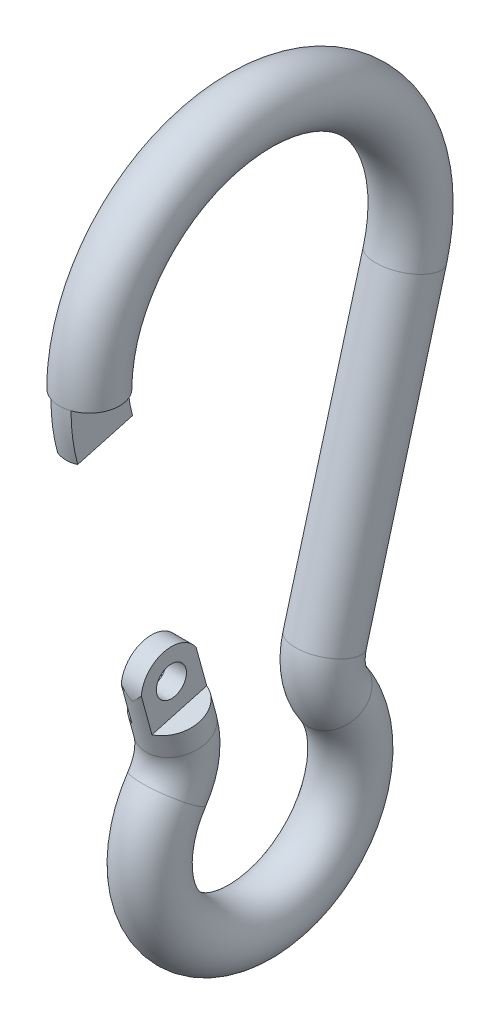
SolidWorks part; units mm, degrees
material "AISI 1020"
ref_plane "Front Plane" through (0, 0, 0) normal (0, 0, 1) x (1, 0, 0)
ref_plane "Top Plane" through (0, 0, 0) normal (0, 1, 0) x (1, 0, 0)
ref_plane "Right Plane" through (0, 0, 0) normal (1, 0, 0) x (0, 0, -1)
sketch "Sketch1" plane through (0, 0, 0) normal (1, 0, 0) x (0, 0, -1)
  line L0 (15.9242, -4.3589) -> (5.7761, -41.4323)
  line L1 (-5.7761, -41.4323) -> (-8.5475, -31.3076)
  line L2 (0, 0) -> (-16.51, 0) construction
  arc A0 (-15.9242, -4.3589) -> (-16.51, 0) centre (0, 0) cw
  arc A1 (5.7761, -41.4323) -> (7.3502, -50.8794) centre (16.8005, -44.45) ccw
  arc A2 (7.3502, -50.8794) -> (-7.3502, -50.8794) centre (0, -55.88) cw
  arc A3 (-7.3502, -50.8794) -> (-5.7761, -41.4323) centre (-16.8005, -44.45) ccw
  arc A4 (-16.51, 0) -> (15.9242, -4.3589) centre (0, 0) cw
  point P11 (-4.5087, 9.6726)
  point P15 (0, 0)
  point P16 (0, 0)
  point P17 (0, 0)
  point P18 (0, 0)
  point P19 (0, 0)
  point P20 (0, 0)
  dimension "D1" = 16.51
  dimension "D4" = 11.43
  dimension "D5" = 8.89
  dimension "D2" = 44.45
  dimension "D3" = 11.43
  dimension "D6" = 27.94
sketch "Sketch2" plane through (0, 0, 0) normal (0, 0, 1) x (1, 0, 0)
  circle A0 centre (0, 20.32) radius 3.81
  point P2 (0, 0)
  dimension "D2" = 7.62
  dimension "D1" = 16.51
sweep "Sweep1" add profiles "Sketch2" path "Sketch1"
sketch "Sketch7" plane through (0, 0, 0) normal (1, 0, 0) x (0, 0, -1)
  line L0 (-24.13, 0) -> (-16.51, 0)
  line L1 (-23.2738, -6.3708) -> (-15.9242, -4.3589)
  line L2 (-15.8972, -33.3194) -> (-8.5475, -31.3076)
  line L3 (-8.5475, -31.3076) -> (-7.5416, -34.9824)
  line L4 (-15.8972, -33.3194) -> (-14.8912, -36.9942)
  line L5 (-11.2164, -35.9883) -> (-14.8912, -36.9942) construction
  line L6 (-14.8912, -36.9942) -> (-13.8853, -40.669)
  line L7 (-15.8972, -33.3194) -> (-13.1257, -43.4441) construction
  line L8 (-13.8853, -40.669) -> (-6.5357, -38.6572)
  line L9 (-5.7761, -41.4323) -> (-8.5475, -31.3076) construction
  line L10 (-6.5357, -38.6572) -> (-7.5416, -34.9824)
  line L11 (-23.2738, -6.3708) -> (-15.9242, -4.3589) construction
  arc A0 (-24.13, 0) -> (-23.2738, -6.3708) centre (0, 0) ccw
  arc A1 (-16.51, 0) -> (-15.9242, -4.3589) centre (0, 0) ccw
  arc A3 (-7.5416, -34.9824) -> (-14.8912, -36.9942) centre (-11.2164, -35.9883) ccw
  circle A4 centre (-11.2164, -35.9883) radius 1.905
  point P16 (0, 0)
  point P23 (-10.9446, -36.9813)
  point P24 (-11.2493, -35.8684)
  dimension "D1" = 3.81
  dimension "D2" = 3.81
  dimension "D3" = 3.81
  dimension "D4" = 31.75
extrude "Cut-Extrude3" cut sketch "Sketch7" along normal through all from offset 1.27 contours A1 L0 A0 L1 | A4 L6 L8 L10 A3 | A3 L2 L4 | A3 L3 L2 region at (0, -2.7301, 20.3144) region at (0, -33.9155, 14.8516) region at (0, -32.3531, 9.1437) region at (0, -32.7828, 9.3887)
mirror "Mirror1" about plane through (0, 0, 0) normal (1, 0, 0) of "Cut-Extrude3"
extrude "Cut-Extrude4" cut sketch "Sketch7<4>" against normal through all both and the other way through all contours A4 | A3 L2 L4 | A3 L3 L2 region at (0, -33.9155, 14.8516) region at (0, -32.3531, 9.1437) region at (0, -35.9883, 11.2164)
sketch "Sketch7<4>" plane through (0, 0, 0) normal (1, 0, 0) x (0, 0, -1) same geometry as "Sketch7"
